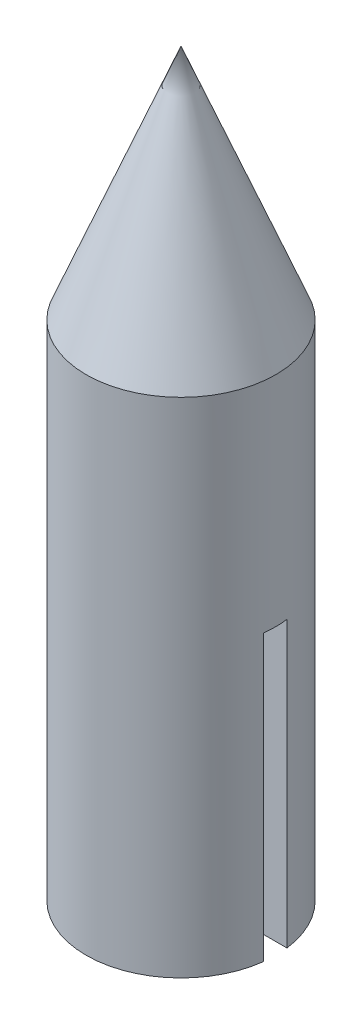
SolidWorks part; units mm, degrees
ref_plane "Front Plane" through (0, 0, 0) normal (0, 0, 1) x (1, 0, 0)
ref_plane "Top Plane" through (0, 0, 0) normal (0, 1, 0) x (1, 0, 0)
ref_plane "Right Plane" through (0, 0, 0) normal (1, 0, 0) x (0, 0, -1)
sketch "Sketch1" plane through (0, 0, 0) normal (0, 1, 0) x (1, 0, 0)
  circle A0 centre (0, 0) radius 2.54
  circle A1 centre (0, 0) radius 1.27
  dimension "D1" = 2.54
  dimension "D2" = 5.08
extrude "Boss-Extrude1" add sketch "Sketch1" along normal blind 11.43
extrude "Boss-Extrude2" add sketch "Sketch1<2>" along normal blind 2.032 from surface contours A1 | A0 A1 region at (-2.4682, 0, 0) region at (0, 0, 0) starting at face at (0, 11.43, 2.54)
sketch "Sketch1<2>" plane through (0, 0, 0) normal (0, 1, 0) x (1, 0, 0) same geometry as "Sketch1"
ref_axis "Axis1" through (0, 13.462, 0) along (0, -1, 0)
sketch "Sketch3" plane through (0, 0, 0) normal (1, 0, 0) x (0, 0, -1)
  line L0 (0, 19.812) -> (2.54, 13.462)
  line L1 (2.54, 13.462) -> (0, 13.462)
  line L2 (0, 13.462) -> (0, 19.812)
  line L3 (2.54, 13.462) -> (-2.54, 13.462) construction
  point P5 (0, 0)
  dimension "D2" = 6.35
revolve "Revolve1" add sketch "Sketch3" angle 360 about axis through (0, 13.462, 0) along (0, -1, 0) region at (0, 15.5787, -0.8467)
sketch "Sketch4" plane through (0, 0, 0) normal (1, 0, 0) x (0, 0, -1)
  line L1 (0.3175, 0) -> (-0.3175, 0)
  line L2 (0.3175, 0) -> (0.3175, 7.62)
  line L3 (0.3175, 7.62) -> (-0.3175, 7.62)
  line L4 (-0.3175, 0) -> (-0.3175, 7.62)
  point P4 (0, 0)
  dimension "D1" = 0.635
  dimension "D2" = 7.62
extrude "Cut-Extrude1" cut sketch "Sketch4" against normal through all both and the other way through all
